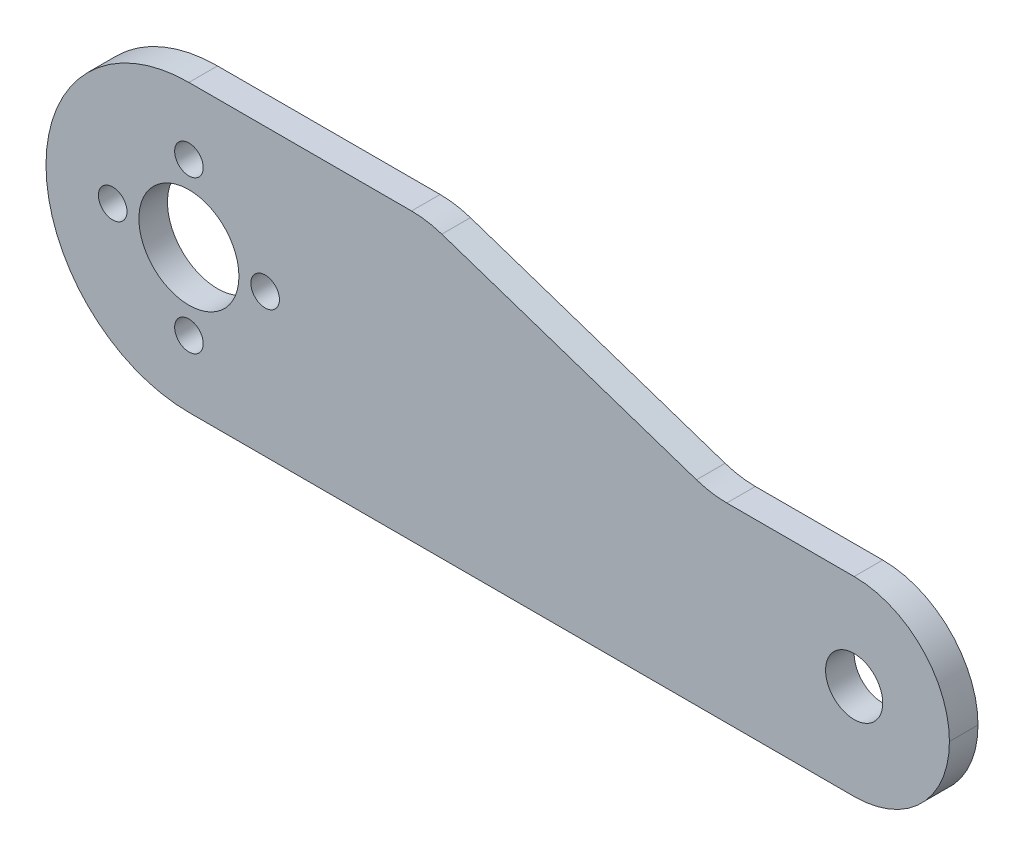
SolidWorks part; units mm, degrees
ref_plane "前视基准面" through (0, 0, 0) normal (0, 0, 1) x (1, 0, 0)
ref_plane "上视基准面" through (0, 0, 0) normal (0, 1, 0) x (1, 0, 0)
ref_plane "右视基准面" through (0, 0, 0) normal (1, 0, 0) x (0, 0, -1)
sketch "草图1" plane through (0, 0, 0) normal (0, 0, 1) x (1, 0, 0)
  line L0 (94.8212, 20) -> (69.8212, 20)
  line L1 (0, 0) -> (94.8212, 0)
  line L2 (0, 0) -> (0, 30)
  line L3 (0, 30) -> (40, 30)
  line L4 (94.8212, 0) -> (94.8212, 20)
  line L5 (69.8212, 20) -> (40, 30)
  circle A0 centre (15, 15) radius 5.25
  circle A1 centre (15, 23) radius 1.5
  circle A2 centre (15, 7) radius 1.5
  circle A3 centre (23, 15) radius 1.5
  circle A4 centre (7, 15) radius 1.5
  circle A5 centre (84.8212, 10) radius 3
  point P15 (0, 15)
  dimension "D1" = 10.5
  dimension "D7" = 15
  dimension "D8" = 3
  dimension "D9" = 6
  dimension "D2" = 30
  dimension "D3" = 16
  dimension "D4" = 8
  dimension "D5" = 8
  dimension "D6" = 8
  dimension "D10" = 70
  dimension "D11" = 10
  dimension "D12" = 20
  dimension "D13" = 20
  dimension "D14" = 25
  dimension "D15" = 40
extrude "凸台-拉伸1" add sketch "草图1" along normal blind 3
fillet "圆角1" radius 10 4 edges at (94.8212, 0, 1.5) (94.8212, 20, 1.5) (69.8212, 20, 1.5) (40, 30, 1.5)
fillet "圆角2" radius 15 2 edges at (0, 0, 1.5) (0, 30, 1.5)
